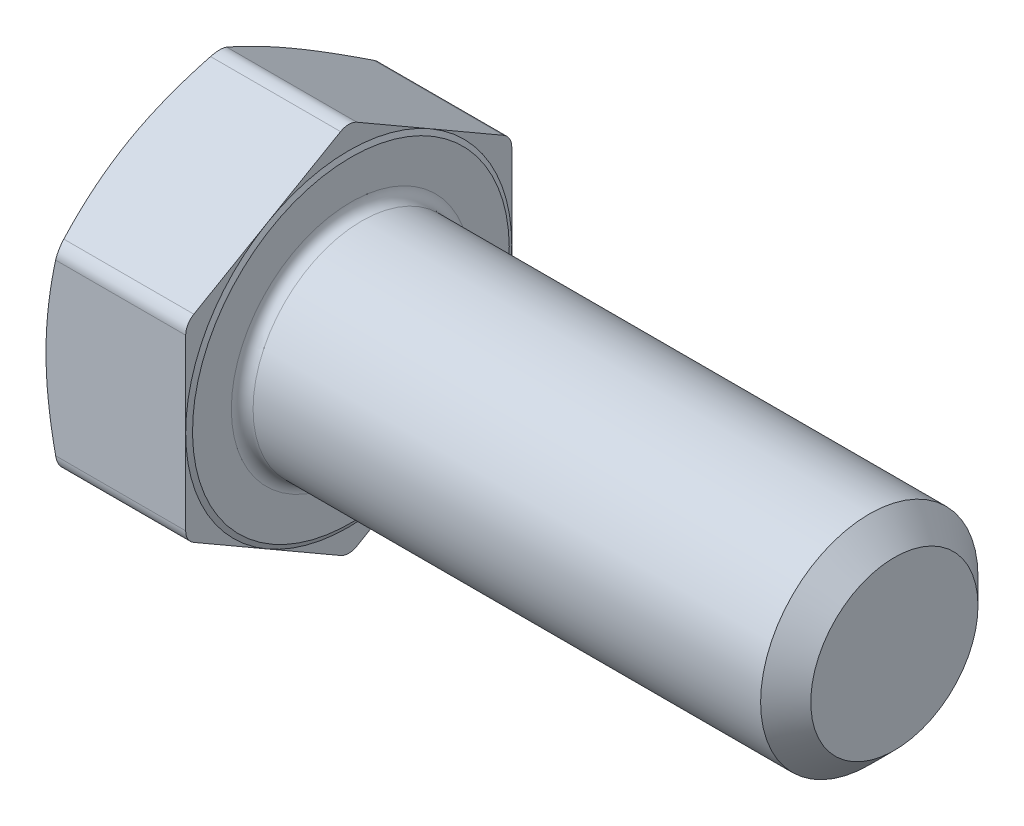
SolidWorks part; units mm, degrees
ref_plane "Front Plane" through (0, 0, 0) normal (0, 0, 1) x (1, 0, 0)
ref_plane "Top Plane" through (0, 0, 0) normal (0, 1, 0) x (1, 0, 0)
ref_plane "Right Plane" through (0, 0, 0) normal (1, 0, 0) x (0, 0, -1)
sketch "Sketch1" plane through (0, 0, 0) normal (0, 0, 1) x (1, 0, 0)
  line L0 (0, 0) -> (31.75, 0) construction
  line L1 (0, 0) -> (-8.7312, 0) construction
  line L2 (0, 9.525) -> (0, -9.525) construction
  line L3 (-8.7312, 9.525) -> (-8.7312, -9.525) construction
  line L4 (31.75, 6.35) -> (31.75, -6.35) construction
  line L8 (29.7962, 6.35) -> (31.75, 6.35) construction
  point P8 (29.7962, 0)
  point P11 (24.9115, -6.35)
  point P12 (1.9538, 0)
  dimension "Head Height" = 8.7312
  dimension "Head Width" = 19.05
  dimension "Length" = 31.75
  dimension "Thread Size" = 12.7
  dimension "D1" = 6.8385
  dimension "Thread Pitch" = 1.9538
  dimension "D2" = 1.9538
sketch "Sketch2" plane through (0, 0, 0) normal (1, 0, 0) x (0, 0, -1)
  circle A0 centre (0, 0) radius 6.35
extrude "Boss-Extrude1" add sketch "Sketch2" along normal up to vertex (31.75 mm away) up to point (31.75, 6.35, 0)
sketch "Sketch3" plane through (0, 0, 0) normal (-1, 0, 0) x (0, 0, 1)
  line L0 (0, 10.9985) -> (0, 0) construction
  line L1 (0, 10.9985) -> (-9.525, 5.4993)
  line L2 (-9.525, 5.4993) -> (-9.525, -5.4993)
  line L3 (-9.525, -5.4993) -> (0, -10.9985)
  line L4 (0, -10.9985) -> (9.525, -5.4993)
  line L5 (9.525, -5.4993) -> (9.525, 5.4993)
  line L6 (9.525, 5.4993) -> (0, 10.9985)
  circle A0 centre (0, 0) radius 9.525 construction
extrude "Boss-Extrude2" add sketch "Sketch3" along normal up to vertex (8.7312 mm away) up to point (-8.7312, 9.525, 0)
sketch "Sketch5" plane through (-8.7312, 0, 0) normal (-1, 0, 0) x (0, 0, 1)
  circle A0 centre (0, 0) radius 9.525 construction
  circle A1 centre (0, 0) radius 9.525 construction
  circle A2 centre (0, 0) radius 8.5725
  dimension "D1" = 0.9525
extrude "Cut-Extrude1" cut sketch "Sketch5" against normal up to vertex (8.7312 mm away) draft 65 flip side to cut up to point (0, 0, 0)
sketch "Sketch11" plane through (-8.7312, 0, 0) normal (-1, 0, 0) x (0, 0, 1)
  line L0 (0, 6.7627) -> (0, 4.191) construction
  line L1 (0.381, 6.7627) -> (0.381, 4.191)
  line L2 (-0.381, 6.7627) -> (-0.381, 4.191)
  arc A0 (0.381, 6.7627) -> (-0.381, 6.7627) centre (0, 6.7627) ccw
  arc A1 (-0.381, 4.191) -> (0.381, 4.191) centre (0, 4.191) ccw
  circle A2 centre (0, 0) radius 7.1438 construction
  circle A3 centre (0, 0) radius 3.81 construction
  point P3 (0, 5.4769)
  dimension "D1" = 14.2875
  dimension "D2" = 7.62
  dimension "D3" = 0.762
extrude "Boss-Extrude5" add sketch "Sketch11" along normal blind 0.0635
fillet "Fillet5" radius 0.0635 4 edges at (-8.7947, 5.4769, 0.381) (-8.7947, 3.81, 0) (-8.7947, 5.4769, -0.381) (-8.7947, 7.1437, 0)
pattern_circular "CirPattern1" count 6 over 360 about axis through (0, 0, 0) along (-1, 0, 0) of "Boss-Extrude5", "Fillet5" reverse direction yes
fillet "Fillet7" radius 0.9525 6 edges at (-3.8, -10.9985, 0) (-3.8, -5.4993, -9.525) (-3.8, 5.4993, -9.525) (-3.8, 10.9985, 0) (-3.8, -5.4993, 9.525) (-3.8, 5.4993, 9.525)
chamfer "Chamfer1" distance 1.4654 angle 45 1 edges at (31.75, 0, -6.35)
sketch "Sketch15" plane through (0, 0, 0) normal (0, 0, 1) x (1, 0, 0)
  line L0 (0, 9.2526) -> (-0.127, 9.525)
  line L1 (0, 9.525) -> (0, -9.525) construction
  line L2 (-0.127, 9.525) -> (-0.127, 10.9985)
  line L3 (-0.127, 10.9985) -> (0, 10.9985)
  line L4 (0, 10.9985) -> (0, 9.2526)
  dimension "D1" = 0.127
  dimension "D2" = 25
revolve "Cut-Revolve1" cut sketch "Sketch15" angle 360 about L1
fillet "Fillet4" radius 0.635 1 edges at (0, 0, 6.35)
sketch "Reference Sketch1" plane through (0, 0, 0) normal (1, 0, 0) x (0, 0, -1)
  line L1 (0, 10.9985) -> (-9.525, 5.4993)
  line L2 (-9.525, 5.4993) -> (-9.525, -5.4993)
  line L3 (-9.525, -5.4993) -> (0, -10.9985)
  line L4 (0, -10.9985) -> (9.525, -5.4993)
  line L5 (9.525, -5.4993) -> (9.525, 5.4993)
  line L6 (9.525, 5.4993) -> (0, 10.9985)
  circle A0 centre (0, 0) radius 9.525 construction
  circle A1 centre (0, 0) radius 9.525
equation "\"D1@Sketch11\"=\"Head Width@Sketch1\" * 0.75"
equation "\"D2@Sketch11\"=\"Head Width@Sketch1\"*0.4"
equation "\"D3@Sketch11\"=\"Head Width@Sketch1\" * .04"
equation "\"D3@Helix/Spiral2\"= \"Length@Sketch1\" + \"Thread Pitch@Sketch1\""
equation "\"D1@Chamfer1\"=\"Thread Pitch@Sketch1\"*0.750"
equation "\"D1@Sketch1\"=\"Thread Pitch@Sketch1\"*3.5"
equation "\"D1@Sketch13\"= \"Thread Pitch@Sketch1\" * 0.125"
equation "\"D1@Sketch5\"=\"Head Width@Sketch1\"*0.05"
equation "\"D1@Fillet4\"=\"Thread Size@Sketch1\"*0.05"
equation "\"D2@Sketch1\"=\"Thread Pitch@Sketch1\""
equation "\"D1@Fillet7\"=\"Head Width@Sketch1\"*0.05"
